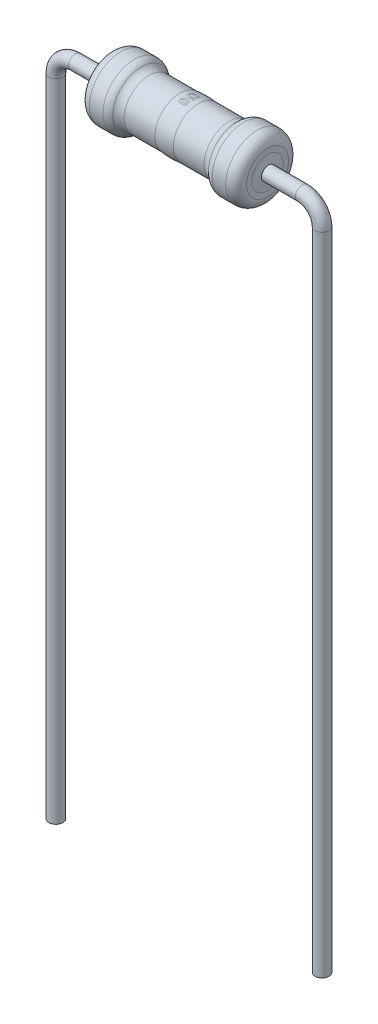
SolidWorks part; units mm, degrees
material "Plain Carbon Steel"
ref_plane "Front Plane" through (0, 0, 0) normal (0, 0, 1) x (1, 0, 0)
ref_plane "Top Plane" through (0, 0, 0) normal (0, 1, 0) x (1, 0, 0)
ref_plane "Right Plane" through (0, 0, 0) normal (1, 0, 0) x (0, 0, -1)
sketch "Sketch1" plane through (0, 0, 0) normal (0, 0, 1) x (1, 0, 0)
  line L0 (-4.33, 0) -> (4.33, 0)
  line L1 (-5.08, -0.75) -> (-5.08, -25.4)
  line L2 (5.08, -0.75) -> (5.08, -25.4)
  line L3 (-5.08, -25.4) -> (5.08, -25.4) construction
  line L4 (0, 0) -> (0, -25.4) construction
  arc A0 (-4.33, 0) -> (-5.08, -0.75) centre (-4.33, -0.75) ccw
  arc A1 (4.33, 0) -> (5.08, -0.75) centre (4.33, -0.75) cw
  dimension "D2" = 0.75
  dimension "D1" = 10.16
  dimension "D3" = 25.4
ref_plane "Plane1" through (-5.08, -25.4, 0) normal (0, -1, 0) x (-1, 0, 0)
sketch "Sketch2" plane through (-5.08, -25.4, 0) normal (0, -1, 0) x (-1, 0, 0)
  circle A0 centre (0, 0) radius 0.265
  dimension "D1" = 0.53
sweep "Sweep1" add profiles "Sketch2" path "Sketch1"
sketch "Sketch3" plane through (0, 0, 0) normal (0, 0, 1) x (1, 0, 0)
  line L0 (-3, 0) -> (3, 0)
  line L5 (-3, 0) -> (-3, 1.2)
  line L6 (3, 0) -> (3, 1.2)
  line L7 (-3, 1.2) -> (-1.75, 1.2)
  line L8 (3, 1.2) -> (1.75, 1.2)
  line L9 (-1.75, 1.2) -> (-1.75, 0.95)
  line L10 (-1.75, 0.95) -> (1.75, 0.95)
  line L11 (1.75, 0.95) -> (1.75, 1.2)
  line L12 (0, 0) -> (0, 0.95) construction
  dimension "D1" = 6
  dimension "D2" = 1.2
  dimension "D3" = 3.5
  dimension "D4" = 0.95
  dimension "D5" = 0.25
revolve "Revolve1" add sketch "Sketch3" angle 360 about L0
fillet "Fillet-1" radius 0.35 2 edges at (1.75, 0, 1.2) (-1.75, 0, 1.2)
fillet "Fillet-2" radius 0.4 4 edges at (3, 0, 1.2) (-3, 0, 1.2) (1.75, 0, 0.95) (-1.75, 0, 0.95)
sketch "Sketch5" plane through (0, 0, 0) normal (0, 0, 1) x (1, 0, 0)
  line L0 (-0.35, 0) -> (0.35, 0)
  line L5 (0, 0) -> (0, 0.95) construction
  line L10 (-0.35, 0.95) -> (0.35, 0.95) construction
  line L15 (-0.35, 0.95) -> (-0.35, 0)
  line L30 (1.5264, 0.95) -> (-1.5264, 0.95) construction
  line L39 (0.35, 0.95) -> (0.35, 0)
  line L41 (0, 0.95) -> (0, 0.97) construction
  line L48 (-3, 0) -> (-3, 0.6)
  line L49 (-3, 0) -> (-3, 1.2) construction
  line L50 (-3, 0) -> (-3.05, 0)
  line L51 (-3.05, 0) -> (-3.05, 0.2)
  line L52 (3, 0) -> (3.05, 0)
  line L53 (3.05, 0) -> (3.05, 0.2)
  line L54 (3, 0) -> (3, 0.6)
  line L55 (3, 0) -> (3, 1.2) construction
  arc A6 (-3, 0.6) -> (-3.05, 0.2) centre (-4.625, 0.6) cw
  arc A7 (3.05, 0.2) -> (3, 0.6) centre (4.625, 0.6) cw
  arc A8 (-0.35, 0.95) -> (0.35, 0.95) centre (0, -2.1025) cw
  dimension "D5" = 0.05
  dimension "D7" = 0.6
  dimension "D8" = 0.7
  dimension "D9" = 0.02
  dimension "D6" = 0.2
revolve "Revolve2" add sketch "Sketch5" angle 360 about L0
ref_plane "Plane2" through (0, 2, 0) normal (0, 1, 0) x (1, 0, 0)
sketch "Sketch6" plane through (0, 2, 0) normal (0, 1, 0) x (1, 0, 0)
  line L0 (-0.35, 0) -> (0.15, 0) construction
  line L1 (0.15, 0.75) -> (0.15, -0.75) construction
  line L3 (-0.35, 0.95) -> (-0.35, -0.95) construction
  text T0 "0Ω" font "Calibri" height 0.3
  dimension "D1" = 0.5
  dimension "D2" = 1.5
wrap "Wrap1" sketch "Sketch6" wrap type scribe source sketch "Sketch6" face at (-0.35, 0, -0.95)
